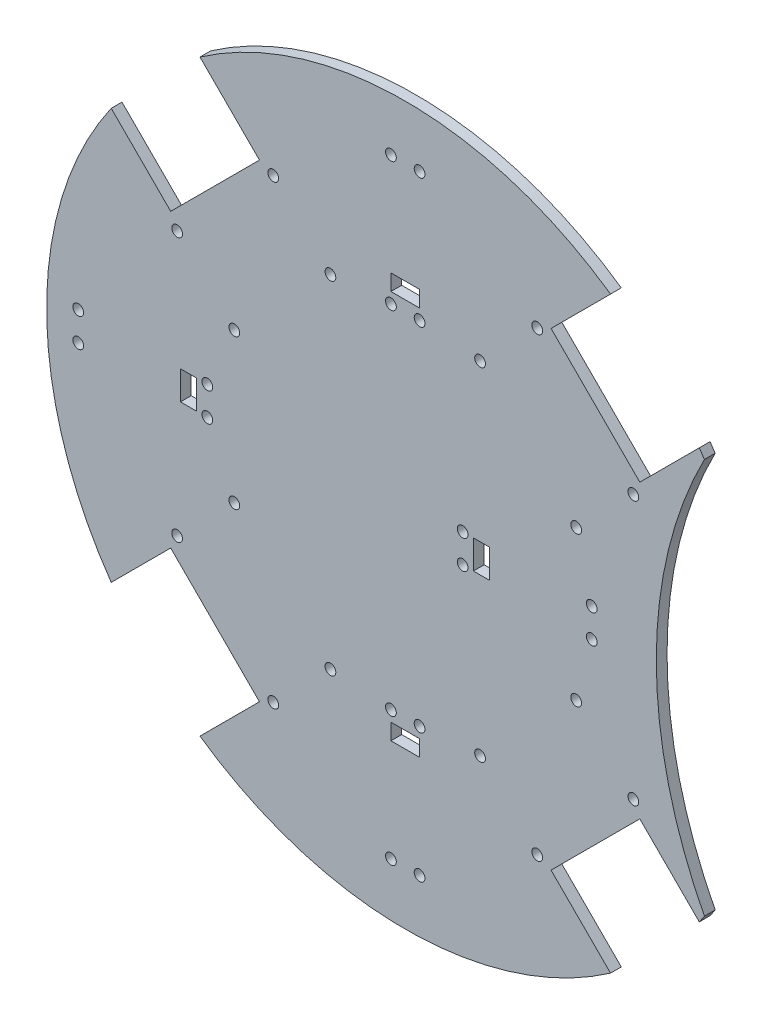
SolidWorks part; units mm, degrees
ref_plane "Alzado" through (0, 0, 0) normal (0, 0, 1) x (1, 0, 0)
ref_plane "Planta" through (0, 0, 0) normal (0, 1, 0) x (1, 0, 0)
ref_plane "Vista lateral" through (0, 0, 0) normal (1, 0, 0) x (0, 0, -1)
sketch "Croquis1" plane through (0, 0, 0) normal (0, 0, 1) x (1, 0, 0)
  circle A0 centre (0, 0) radius 100
  dimension "D1" = 200
extrude "Saliente-Extruir1" add sketch "Croquis1" along normal blind 3
sketch "Croquis3" plane through (0, 0, 3) normal (0, 0, 1) x (1, 0, 0)
  line L0 (0, 0) -> (190, 0) construction
  circle A0 centre (190, 0) radius 120
  dimension "D1" = 240
  dimension "D2" = 190
extrude "Cortar-Extruir1" cut sketch "Croquis3" against normal blind 3
sketch "Croquis5" plane through (0, 0, 3) normal (0, 0, 1) x (1, 0, 0)
  line L0 (0, -100) -> (0, 100) construction
  line L1 (-100, 0) -> (70, 0) construction
  line L2 (0, 0) -> (-70.7107, -70.7107) construction
  line L3 (-70.7107, -70.7107) -> (70.7107, 70.7107) construction
  line L4 (0, 0) -> (-70.7107, 70.7107) construction
  line L5 (-70.7107, 70.7107) -> (70.7107, -70.7107) construction
  line L6 (-70.7107, -70.7107) -> (-58.3363, -83.085) construction
  line L9 (-58.3363, -83.085) -> (-83.085, -58.3363)
  line L11 (-83.085, -58.3363) -> (-65.4074, -40.6586)
  line L12 (-65.4074, -40.6586) -> (-40.6586, -65.4074)
  line L13 (-40.6586, -65.4074) -> (-58.3363, -83.085)
  line L14 (-70.7107, 70.7107) -> (-83.085, 58.3363) construction
  line L15 (-83.085, 58.3363) -> (-100, 0) construction
  line L17 (-83.085, 58.3363) -> (-58.3363, 83.085)
  line L18 (-58.3363, 83.085) -> (-40.6586, 65.4074)
  line L19 (-40.6586, 65.4074) -> (-65.4074, 40.6586)
  line L20 (-65.4074, 40.6586) -> (-83.085, 58.3363)
  line L22 (70.7107, -70.7107) -> (58.3363, -83.085) construction
  line L23 (58.3363, -83.085) -> (0, -100) construction
  line L24 (58.3363, -83.085) -> (83.085, -58.3363)
  line L25 (83.085, -58.3363) -> (65.4074, -40.6586)
  line L26 (65.4074, -40.6586) -> (40.6586, -65.4074)
  line L27 (40.6586, -65.4074) -> (58.3363, -83.085)
  line L28 (70.7107, 70.7107) -> (58.3363, 83.085) construction
  line L29 (58.3363, 83.085) -> (0, 100) construction
  line L30 (58.3363, 83.085) -> (83.085, 58.3363)
  line L31 (83.085, 58.3363) -> (65.4074, 40.6586)
  line L32 (65.4074, 40.6586) -> (40.6586, 65.4074)
  line L33 (40.6586, 65.4074) -> (58.3363, 83.085)
  arc A0 (83.4211, 55.1446) -> (83.4211, -55.1446) centre (0, 0) ccw construction
  arc A1 (83.4211, 55.1446) -> (83.4211, -55.1446) centre (190, 0) ccw construction
  point P36 (0, 0)
  dimension "D2" = 17.5
  dimension "D3" = 25
  dimension "D4" = 35
  dimension "D5" = 25
  dimension "D6" = 35
  dimension "D8" = 25
  dimension "D9" = 17.5
  dimension "D7" = 35
  dimension "D10" = 90
  dimension "D11" = 17.5
  dimension "D12" = 17.5
  dimension "D13" = 35
  dimension "D14" = 25
  dimension "D15" = 134.3503
  dimension "D16" = 100
extrude "Cortar-Extruir6" cut sketch "Croquis5" against normal blind 10
sketch "Croquis12" plane through (0, 0, 3) normal (0, 0, 1) x (1, 0, 0)
  line L0 (-53.033, -53.033) -> (-39.9421, -50.0116) construction
  line L1 (-40.6586, -65.4074) -> (-65.4074, -40.6586) construction
  line L2 (-39.9421, -50.0116) -> (-36.8049, -63.6043) construction
  line L3 (-36.8049, -63.6043) -> (-63.6043, -36.8049) construction
  line L4 (-63.6043, -36.8049) -> (-47.6661, -20.8667) construction
  line L6 (53.033, -53.033) -> (-53.033, 53.033) construction
  line L7 (65.4074, -40.6586) -> (40.6586, -65.4074) construction
  line L8 (-65.4074, 40.6586) -> (-40.6586, 65.4074) construction
  line L9 (36.8049, 63.6043) -> (20.8667, 47.6661) construction
  line L10 (63.6043, 36.8049) -> (36.8049, 63.6043) construction
  line L11 (50.0116, 39.9421) -> (63.6043, 36.8049) construction
  line L12 (53.033, 53.033) -> (50.0116, 39.9421) construction
  line L14 (53.033, -53.033) -> (50.2046, -50.2046) construction
  line L15 (50.2046, -50.2046) -> (36.8049, -63.6043) construction
  line L16 (36.8049, -63.6043) -> (63.6043, -36.8049) construction
  line L17 (63.6043, -36.8049) -> (47.6661, -20.8667) construction
  line L19 (-53.033, -53.033) -> (53.033, 53.033) construction
  line L20 (-36.8049, 63.6043) -> (-20.8667, 47.6661) construction
  line L21 (-63.6043, 36.8049) -> (-36.8049, 63.6043) construction
  line L22 (-50.2046, 50.2046) -> (-63.6043, 36.8049) construction
  line L23 (-53.033, 53.033) -> (-50.2046, 50.2046) construction
  circle A0 centre (-63.6043, -36.8049) radius 1.5
  circle A1 centre (-36.8049, -63.6043) radius 1.5
  circle A2 centre (-47.6661, -20.8667) radius 1.5
  circle A3 centre (-20.8667, -47.6661) radius 1.5
  circle A5 centre (47.6661, 20.8667) radius 1.5
  circle A6 centre (20.8667, 47.6661) radius 1.5
  circle A7 centre (63.6043, 36.8049) radius 1.5
  circle A8 centre (36.8049, 63.6043) radius 1.5
  circle A10 centre (20.8667, -47.6661) radius 1.5
  circle A11 centre (47.6661, -20.8667) radius 1.5
  circle A12 centre (63.6043, -36.8049) radius 1.5
  circle A13 centre (36.8049, -63.6043) radius 1.5
  circle A15 centre (-63.6043, 36.8049) radius 1.5
  circle A16 centre (-36.8049, 63.6043) radius 1.5
  circle A17 centre (-20.8667, 47.6661) radius 1.5
  circle A18 centre (-47.6661, 20.8667) radius 1.5
  dimension "D2" = 3
  dimension "D3" = 3
  dimension "D4" = 4
  dimension "D5" = 4
  dimension "D6" = 3
  dimension "D7" = 3
  dimension "D8" = 37.9
  dimension "D9" = 22.54
  dimension "D10" = 22.54
  dimension "D11" = 37.9
  dimension "D12" = 18.95
  dimension "D13" = 18.95
  dimension "D14" = 3
  dimension "D15" = 3
  dimension "D16" = 3
  dimension "D17" = 3
  dimension "D18" = 37.9
  dimension "D19" = 22.54
  dimension "D20" = 22.54
  dimension "D21" = 37.9
  dimension "D22" = 4
  dimension "D1" = 13.95
extrude "Cortar-Extruir7" cut sketch "Croquis12" against normal through all
sketch "Croquis9" plane through (0, 0, 3) normal (0, 0, 1) x (1, 0, 0)
  line L0 (0, 0) -> (-100, 0) construction
  line L5 (0, 100) -> (0, -100) construction
  line L6 (19, 4) -> (23.5, 4)
  line L7 (19, 4) -> (19, -4)
  line L8 (19, -4) -> (23.5, -4)
  line L9 (23.5, 4) -> (23.5, -4)
  line L10 (-4, -52) -> (4, -52)
  line L11 (-58.1901, 4) -> (-62.6901, 4)
  line L12 (-58.1901, 4) -> (-58.1901, -4)
  line L13 (-58.1901, -4) -> (-62.6901, -4)
  line L14 (-62.6901, 4) -> (-62.6901, -4)
  line L15 (-4, 56.5) -> (4, 56.5)
  line L16 (-4, 56.5) -> (-4, 52)
  line L17 (-4, 52) -> (4, 52)
  line L18 (4, 56.5) -> (4, 52)
  line L19 (4, -56.5) -> (4, -52)
  line L20 (-4, -56.5) -> (4, -56.5)
  line L21 (-4, -56.5) -> (-4, -52)
  line L22 (0, 0) -> (70, 0) construction
  line L24 (-58.2511, -4) -> (-58.2738, -4) construction
  circle A0 centre (52, -4) radius 1.5
  circle A1 centre (16, 4) radius 1.5
  circle A4 centre (52, 4) radius 1.5
  circle A5 centre (16, -4) radius 1.5
  arc A6 (-81.9939, 57.2451) -> (-81.9939, -57.2451) centre (0, 0) ccw construction
  arc A7 (83.4211, 55.1446) -> (83.4211, -55.1446) centre (190, 0) ccw construction
  circle A8 centre (-91.1901, 4) radius 1.5
  circle A9 centre (-91.1901, -4) radius 1.5
  circle A10 centre (-55.1901, 4) radius 1.5
  circle A11 centre (-55.1901, -4) radius 1.5
  circle A12 centre (-4, 85) radius 1.5
  circle A13 centre (4, 85) radius 1.5
  circle A14 centre (-4, 49) radius 1.5
  circle A15 centre (4, 49) radius 1.5
  circle A20 centre (-4, -49) radius 1.5
  circle A21 centre (4, -49) radius 1.5
  circle A22 centre (4, -85) radius 1.5
  circle A23 centre (-4, -85) radius 1.5
  arc A25 (57.2451, 81.9939) -> (-57.2451, 81.9939) centre (0, 0) ccw construction
  dimension "D6" = 16
  dimension "D7" = 3
  dimension "D8" = 36
  dimension "D9" = 36
  dimension "D10" = 3
  dimension "D11" = 3
  dimension "D12" = 4
  dimension "D13" = 4
  dimension "D14" = 3
  dimension "D15" = 3
  dimension "D16" = 3
  dimension "D21" = 4
  dimension "D22" = 4
  dimension "D23" = 3
  dimension "D24" = 3
  dimension "D25" = 4
  dimension "D26" = 4
  dimension "D27" = 36
  dimension "D28" = 36
  dimension "D29" = 91.1901
  dimension "D30" = 91.1901
  dimension "D35" = 3
  dimension "D36" = 3
  dimension "D37" = 8
  dimension "D38" = 4
  dimension "D39" = 3
  dimension "D40" = 3
  dimension "D41" = 8
  dimension "D42" = 36
  dimension "D43" = 36
  dimension "D44" = 36
  dimension "D45" = 4
  dimension "D46" = 4
  dimension "D51" = 4
  dimension "D52" = 4
  dimension "D53" = 16
  dimension "D55" = 36
  dimension "D56" = 49
  dimension "D57" = 49
  dimension "D58" = 3
  dimension "D59" = 3
  dimension "D60" = 3
  dimension "D61" = 3
  dimension "D62" = 4.5
  dimension "D32" = 8
  dimension "D64" = 0
  dimension "D69" = 8
  dimension "D70" = 4
  dimension "D71" = 85.0941
  dimension "D72" = 85.0941
  dimension "D17" = 4.5
  dimension "D18" = 8
  dimension "D19" = 3
  dimension "D20" = 0
  dimension "D31" = 3.061
  dimension "D33" = 3
  dimension "D34" = 0
  dimension "D47" = 8
  dimension "D48" = 4.5
  dimension "D49" = 0
  dimension "D50" = 3
  dimension "D54" = 4
  dimension "D63" = 0
  dimension "D65" = 3
  dimension "D66" = 4.5
  dimension "D67" = 8
  dimension "D68" = 3
extrude "Cortar-Extruir5" cut sketch "Croquis9" against normal blind 10
